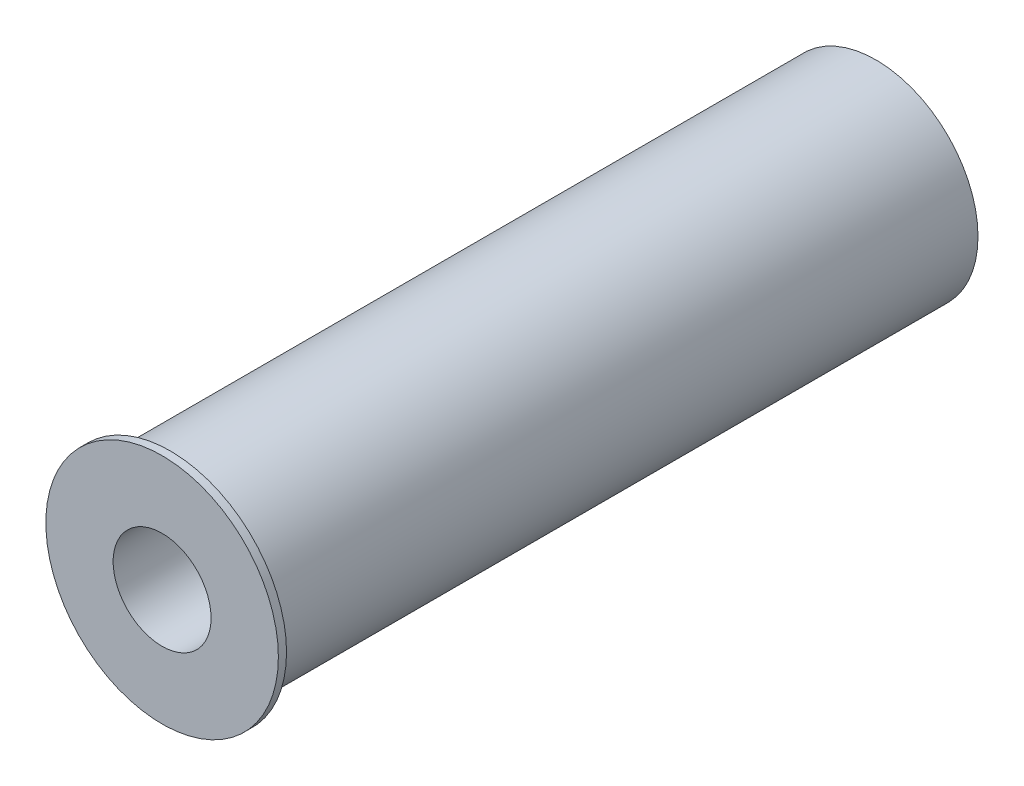
SolidWorks part; units mm, degrees
ref_plane "Ebene vorne" through (0, 0, 0) normal (0, 0, 1) x (1, 0, 0)
ref_plane "Ebene oben" through (0, 0, 0) normal (0, 1, 0) x (1, 0, 0)
ref_plane "Ebene rechts" through (0, 0, 0) normal (1, 0, 0) x (0, 0, -1)
sketch "Skizze1" plane through (0, 0, 0) normal (0, 0, 1) x (1, 0, 0)
  circle A0 centre (0, 0) radius 12.5
  circle A1 centre (0, 0) radius 6
  dimension "D1" = 25
extrude "Aufsatz-Linear austragen1" add sketch "Skizze1" along normal blind 86.5
sketch "Skizze2" plane through (0, 0, 86.5) normal (0, 0, 1) x (1, 0, 0)
  circle A0 centre (0, 0) radius 6
  circle A1 centre (0, 0) radius 14.25
  dimension "D1" = 28.5
extrude "Aufsatz-Linear austragen2" add sketch "Skizze2" along normal blind 1
sketch "Skizze3" plane through (0, 0, 0) normal (0, 0, -1) x (-1, 0, 0)
  line L0 (6, 0) -> (12.5, 0) construction
  circle A0 centre (0, 0) radius 6
  circle A1 centre (0, 0) radius 12.5
  circle A2 centre (9.25, 0) radius 1.65
  circle A3 centre (4.625, -8.0107) radius 1.65
  circle A4 centre (-4.625, -8.0107) radius 1.65
  circle A5 centre (-9.25, 0) radius 1.65
  circle A6 centre (-4.625, 8.0107) radius 1.65
  circle A7 centre (4.625, 8.0107) radius 1.65
  point P20 (0, 0)
  dimension "D1" = 6
extrude "Schnitt-Linear austragen1" cut sketch "Skizze3" against normal blind 15 contours A7 | A2 L0 | L0 A2 | A3 | A4 | A5 | A6 region at (-9.25, -0.7003, 0) region at (-9.25, 0.7003, 0) region at (-4.625, -8.0107, 0) region at (4.625, -8.0107, 0) region at (9.25, 0, 0) region at (-4.625, 8.0107, 0)
